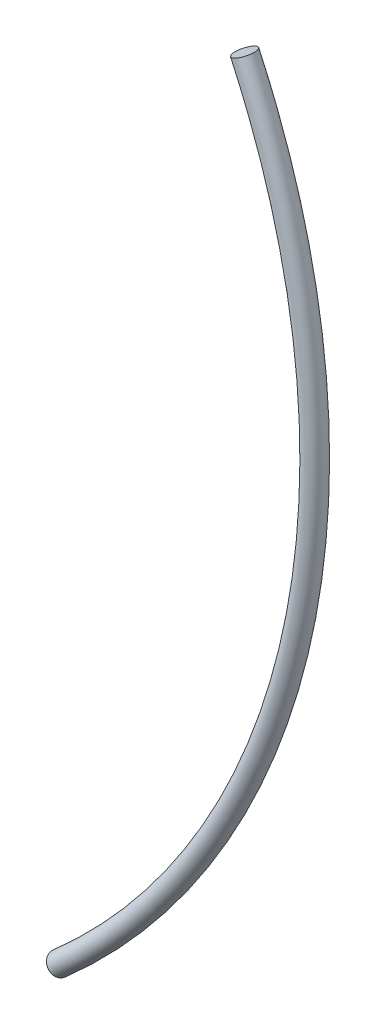
SolidWorks part; units mm, degrees
material "Aço cromo inoxidável"
ref_plane "Plano frontal" through (0, 0, 0) normal (0, 0, 1) x (1, 0, 0)
ref_plane "Plano superior" through (0, 0, 0) normal (0, 1, 0) x (1, 0, 0)
ref_plane "Plano direito" through (0, 0, 0) normal (1, 0, 0) x (0, 0, -1)
sketch "Esboço1" plane through (0, 0, 0) normal (0, 0, 1) x (1, 0, 0)
  line L0 (98.3913, 58.6907) -> (200.7619, 82.0412) construction
  line L1 (165.0792, 66.2094) -> (172.0404, 67.7972) construction
  line L2 (163.4113, 73.5216) -> (166.747, 58.8972) construction
  line L3 (173.7083, 60.485) -> (170.3725, 75.1094) construction
  arc A0 (114.6659, -117.0063) -> (158.8448, 92.9937) centre (-3.5, 17.5) ccw
  circle A1 centre (-3.5, 17.5) radius 1.5 construction
  point P11 (168.5598, 67.0033)
  dimension "D1" = 210
  dimension "D2" = 20
sweep "Varredura1" add path "Esboço1" circular profile diameter 5 parameters "D3"=5
